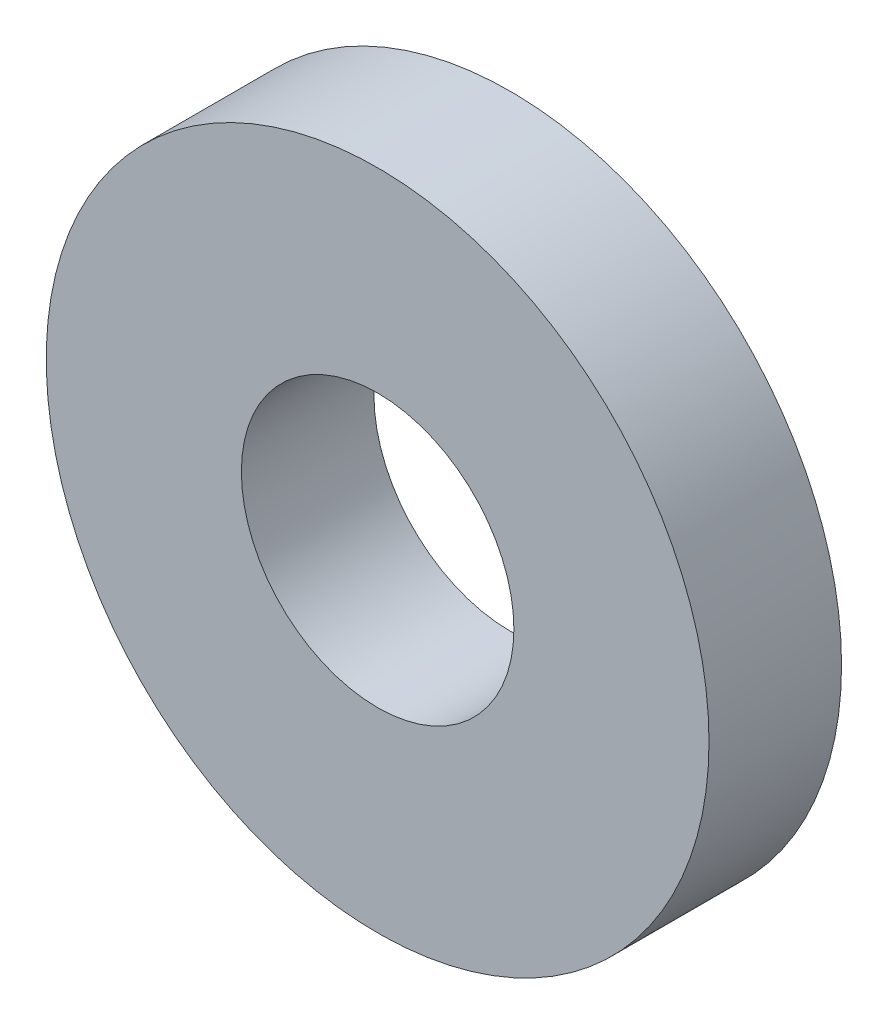
SolidWorks part; units mm, degrees
ref_plane "Front Plane" through (0, 0, 0) normal (0, 0, 1) x (1, 0, 0)
ref_plane "Top Plane" through (0, 0, 0) normal (0, 1, 0) x (1, 0, 0)
ref_plane "Right Plane" through (0, 0, 0) normal (1, 0, 0) x (0, 0, -1)
sketch "Sketch1" plane through (0, 0, 0) normal (1, 0, 0) x (0, 0, -1)
  line L0 (-1.5875, -3.2639) -> (-1.5875, 3.2639) construction
  line L1 (1.5875, -7.9375) -> (-1.5875, -7.9375) construction
  line L2 (1.5875, -7.9375) -> (1.5875, 7.9375) construction
  line L3 (1.5875, 7.9375) -> (-1.5875, 7.9375) construction
  line L4 (-1.5875, -7.9375) -> (-1.5875, 7.9375) construction
  line L5 (0, 7.9375) -> (0, -7.9375) construction
  line L6 (1.5875, 0) -> (-1.5875, 0) construction
  point P0 (0, 0)
  point P7 (-1.5875, 0)
  dimension "D1" = 6.5278
  dimension "D2" = 15.875
sketch "Sketch3" plane through (0, 0, 0) normal (0, 0, 1) x (1, 0, 0)
  circle A0 centre (0, 0) radius 3.2639 construction
  circle A1 centre (0, 0) radius 7.9375 construction
  point P6 (0, -3.2639)
  dimension "OD" = 15.875
  dimension "ID" = 6.5278
sketch "Sketch2" plane through (0, 0, 0) normal (0, 0, 1) x (1, 0, 0)
  circle A0 centre (0, 0) radius 7.9375
  circle A1 centre (0, 0) radius 3.2639
extrude "Extrude1" add sketch "Sketch2" along normal up to vertex and the other way up to vertex up to point (0, -7.9375, 1.5875) other way up to point (0, 7.9375, -1.5875)
equation "\"D1@Sketch1\"=\"ID@Sketch3\""
equation "\"D2@Sketch1\"=\"OD@Sketch3\""
